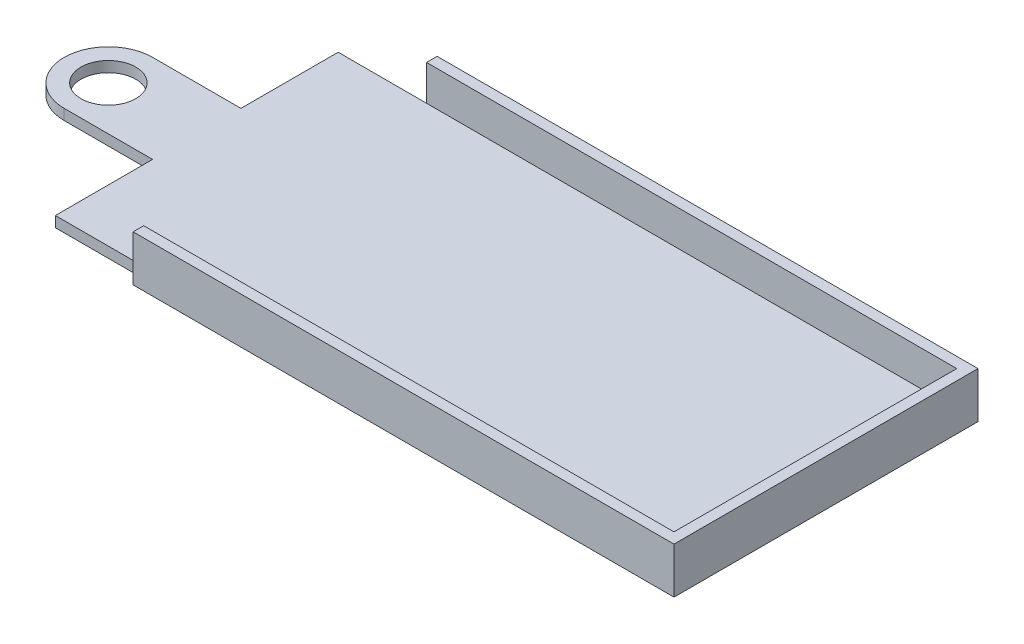
SolidWorks part; units mm, degrees
ref_plane "Front Plane" through (0, 0, 0) normal (0, 0, 1) x (1, 0, 0)
ref_plane "Top Plane" through (0, 0, 0) normal (0, 1, 0) x (1, 0, 0)
ref_plane "Right Plane" through (0, 0, 0) normal (1, 0, 0) x (0, 0, -1)
sketch "Sketch1" plane through (0, 0, 0) normal (0, 1, 0) x (1, 0, 0)
  line L1 (30, -16) -> (-30, -16)
  line L2 (30, -16) -> (30, 16)
  line L3 (30, 16) -> (-30, 16)
  line L4 (-30, -16) -> (-30, 16)
  line L5 (30, -16) -> (-30, 16) construction
  line L6 (30, 16) -> (-30, -16) construction
  point P0 (0, 0)
  dimension "D1" = 60
  dimension "D2" = 32
extrude "Boss-Extrude1" add sketch "Sketch1" along normal blind 1.2
sketch "Sketch2" plane through (0, 0, 0) normal (0, -1, 0) x (1, 0, 0)
  line L1 (-30, -17.2) -> (31.2, -17.2)
  line L2 (31.2, -17.2) -> (31.2, 17.2)
  line L3 (31.2, 17.2) -> (-30, 17.2)
  line L4 (-30, 16) -> (-30, -16)
  line L5 (-30, -16) -> (30, -16)
  line L6 (30, -16) -> (30, 16)
  line L7 (30, 16) -> (-30, 16)
  line L9 (-30, -16) -> (30, -16)
  line L10 (30, -16) -> (30, 16)
  line L11 (30, 16) -> (-30, 16)
  line L12 (-31.2, 17.2) -> (-31.2, -17.2) construction
  line L13 (-30, 16) -> (-30, -16) construction
  line L14 (-30, 16) -> (-30, 17.2)
  line L15 (-30, -16) -> (-30, -17.2)
  line L17 (31.2, 17.2) -> (-31.2, 17.2) construction
  line L18 (-31.2, -17.2) -> (31.2, -17.2) construction
  dimension "D1" = 0
  dimension "D2" = 1.2
extrude "Boss-Extrude2" add sketch "Sketch2" along direction (0, -1, 0) on the side against the normal offset from surface (5.2 mm away) 4 up to face at (0, 1.2, 0) offset beyond the face yes
sketch "Sketch3" plane through (0, 0, 0) normal (0, -1, 0) x (1, 0, 0)
  line L0 (-30, -17.2) -> (-30, 17.2) construction
  line L1 (-30, -16) -> (-40, -16)
  line L2 (-30, -16) -> (-30, 16)
  line L3 (-30, 16) -> (-40, 16)
  line L4 (-40, -16) -> (-40, 16)
  point P6 (-30, 0)
  point P7 (-30, 0)
  dimension "D1" = 32
  dimension "D2" = 10
extrude "Boss-Extrude3" add sketch "Sketch3" against normal up to surface (1.2 mm away) up to face at (0, 1.2, 0)
sketch "Sketch4" plane through (0, 0, 0) normal (0, -1, 0) x (1, 0, 0)
  line L0 (-40, 16) -> (-40, -16) construction
  line L1 (-40, -5) -> (-55, -5)
  line L2 (-40, -5) -> (-40, 5)
  line L3 (-40, 5) -> (-55, 5)
  line L4 (-55, -5) -> (-55, 5)
  point P6 (-40, 0)
  point P7 (-40, 0)
  dimension "D1" = 15
  dimension "D2" = 10
extrude "Boss-Extrude4" add sketch "Sketch4" against normal up to surface (1.2 mm away) up to face at (-13.3333, 1.2, 0)
fillet "Fillet1" radius 5 2 edges at (-55, 0.6, 5) (-55, 0.6, -5)
sketch "Sketch5" plane through (0, 0, 0) normal (0, -1, 0) x (1, 0, 0)
  circle A0 centre (-50, 0) radius 3.1
  dimension "D1" = 6.2
extrude "Cut-Extrude1" cut sketch "Sketch5" against normal up to next
